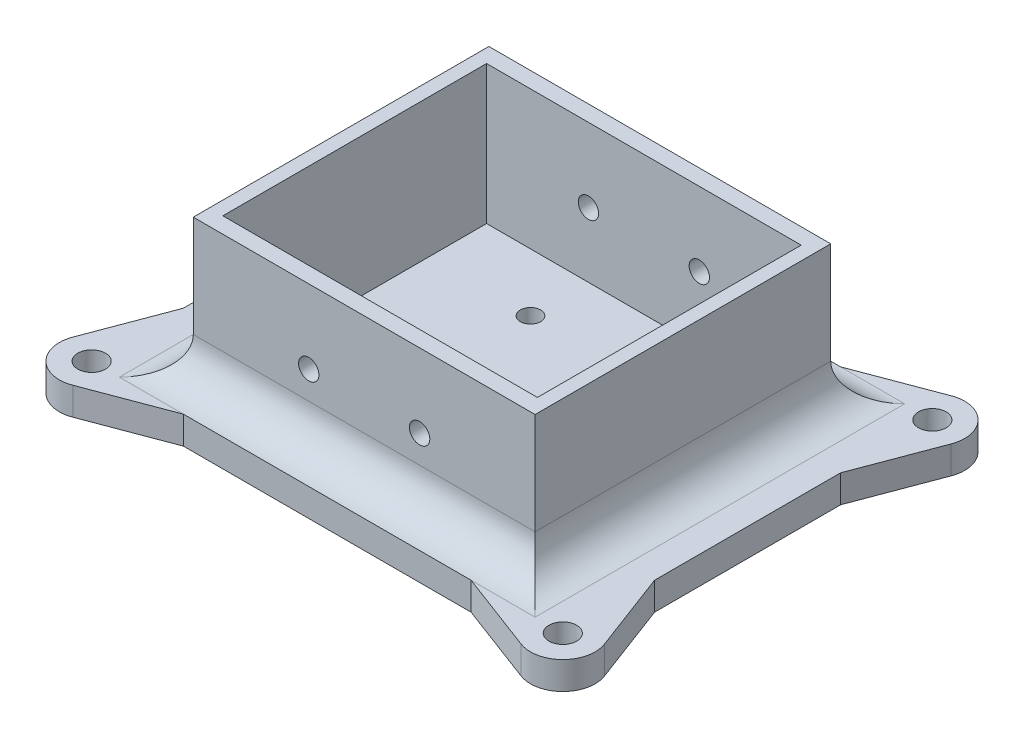
SolidWorks part; units mm, degrees
ref_plane "前视基准面" through (0, 0, 0) normal (0, 0, 1) x (1, 0, 0)
ref_plane "上视基准面" through (0, 0, 0) normal (0, 1, 0) x (1, 0, 0)
ref_plane "右视基准面" through (0, 0, 0) normal (1, 0, 0) x (0, 0, -1)
other "Configuration Table"
sketch "Sketch1" plane through (0, 0, 0) normal (0, 1, 0) x (1, 0, 0)
  line L0 (-24.2665, 23.2754) -> (-15.5689, 20)
  line L10 (24.2665, 23.2754) -> (15.5689, 20)
  line L11 (24.2665, -23.2754) -> (15.5689, -20)
  line L12 (-24.2665, -23.2754) -> (-15.5689, -20)
  line L13 (-28.7754, 18.7665) -> (-25.5, 10.0689)
  line L14 (28.7754, 18.7665) -> (25.5, 10.0689)
  line L15 (28.7754, -18.7665) -> (25.5, -10.0689)
  line L16 (-28.7754, -18.7665) -> (-25.5, -10.0689)
  line L17 (-25.5, 10.0689) -> (-25.5, -10.0689)
  line L18 (-15.5689, 20) -> (15.5689, 20)
  line L20 (25.5, 10.0689) -> (25.5, -10.0689)
  line L24 (-15.5689, -20) -> (15.5689, -20)
  circle A0 centre (-25.5, 20) radius 1.5
  circle A1 centre (25.5, 20) radius 1.5
  circle A2 centre (25.5, -20) radius 1.5
  circle A3 centre (-25.5, -20) radius 1.5
  arc A4 (-24.2665, 23.2754) -> (-28.7754, 18.7665) centre (-25.5, 20) ccw
  arc A5 (28.7754, 18.7665) -> (24.2665, 23.2754) centre (25.5, 20) ccw
  arc A6 (24.2665, -23.2754) -> (28.7754, -18.7665) centre (25.5, -20) ccw
  arc A7 (-28.7754, -18.7665) -> (-24.2665, -23.2754) centre (-25.5, -20) ccw
  point P0 (0, 0)
  dimension "D1" = 40
  dimension "D2" = 51
extrude "Boss-Extrude2" add sketch "Sketch1" along normal blind 3
sketch "Sketch2" plane through (0, 3, 0) normal (0, 1, 0) x (1, 0, 0)
  line L1 (-17.025, 14.275) -> (17.025, 14.275)
  line L2 (-17.025, 14.275) -> (-17.025, -14.275)
  line L3 (-17.025, -14.275) -> (17.025, -14.275)
  line L4 (17.025, 14.275) -> (17.025, -14.275)
  line L5 (0, -14.275) -> (0, 14.275) construction
  line L6 (-17.025, 0) -> (17.025, 0) construction
  line L7 (-18.5, 16) -> (18.5, 16)
  line L8 (-18.5, 16) -> (-18.5, -16)
  line L9 (-18.5, -16) -> (18.5, -16)
  line L10 (18.5, 16) -> (18.5, -16)
  line L11 (0, -16) -> (0, 16) construction
  line L12 (-18.5, 0) -> (18.5, 0) construction
  line L13 (-6, 8) -> (6, 8)
  line L14 (-6, 8) -> (-6, -8)
  line L15 (-6, -8) -> (6, -8)
  line L16 (6, 8) -> (6, -8)
  line L17 (0, -8) -> (0, 8) construction
  line L18 (-6, 0) -> (6, 0) construction
  circle A0 centre (-6, 8) radius 1.1
  circle A1 centre (6, 8) radius 1.1
  circle A2 centre (6, -8) radius 1.1
  circle A3 centre (-6, -8) radius 1.1
  point P0 (0, 0)
  point P4 (0, 0)
  point P11 (0, 0)
  dimension "D1" = 28.55
  dimension "D2" = 34.05
  dimension "D3" = 32
  dimension "D4" = 37
  dimension "D5" = 16
  dimension "D6" = 12
extrude "Boss-Extrude3" add sketch "Sketch2" along normal blind 15 contours L10 L7 L8 L9 L1 L4 L3 L2 region at (0, 3, -15.5108)
sketch "Sketch3" plane through (0, 0, -14.275) normal (0, 0, 1) x (1, 0, 0)
  line L0 (-17.025, 3) -> (17.025, 3) construction
  line L1 (-6, -4) -> (6, -4)
  line L2 (-6, -4) -> (-6, 10)
  line L3 (-6, 10) -> (6, 10)
  line L4 (6, -4) -> (6, 10)
  line L5 (0, 10) -> (0, -4) construction
  line L6 (-6, 3) -> (6, 3) construction
  circle A0 centre (-6, 10) radius 1.1
  circle A1 centre (6, 10) radius 1.1
  point P0 (0, 3)
  dimension "D1" = 14
  dimension "D2" = 12
extrude "Cut-Extrude1" cut sketch "Sketch3" against normal blind 11 and the other way blind 40 contours L3 A0 L2 | L2 A0 L3 | L4 A1 L3 | L3 A1 L4 region at (-6.1556, 10.1556, -14.275) region at (-5.5331, 9.5331, -14.275) region at (5.5331, 9.5331, -14.275) region at (6.1556, 10.1556, -14.275)
extrude "Cut-Extrude2" cut sketch "Sketch2<4>" against normal blind 11 contours A0 | A1 | A2 | A3
sketch "Sketch2<4>" plane through (0, 3, 0) normal (0, 1, 0) x (1, 0, 0) same geometry as "Sketch2"
sketch "Sketch4" plane through (0, 0, 0) normal (0, -1, 0) x (1, 0, 0)
  circle A0 centre (6, 8) radius 2
  circle A1 centre (6, -8) radius 2
  circle A2 centre (-6, -8) radius 2
  circle A3 centre (-6, 8) radius 2
extrude "Cut-Extrude3" [suppressed] cut sketch "Sketch4" against normal blind 2
fillet "Fillet1" radius 4 4 edges at (-18.5, 3, 0) (0, 3, -16) (0, 3, 16) (18.5, 3, 0)
